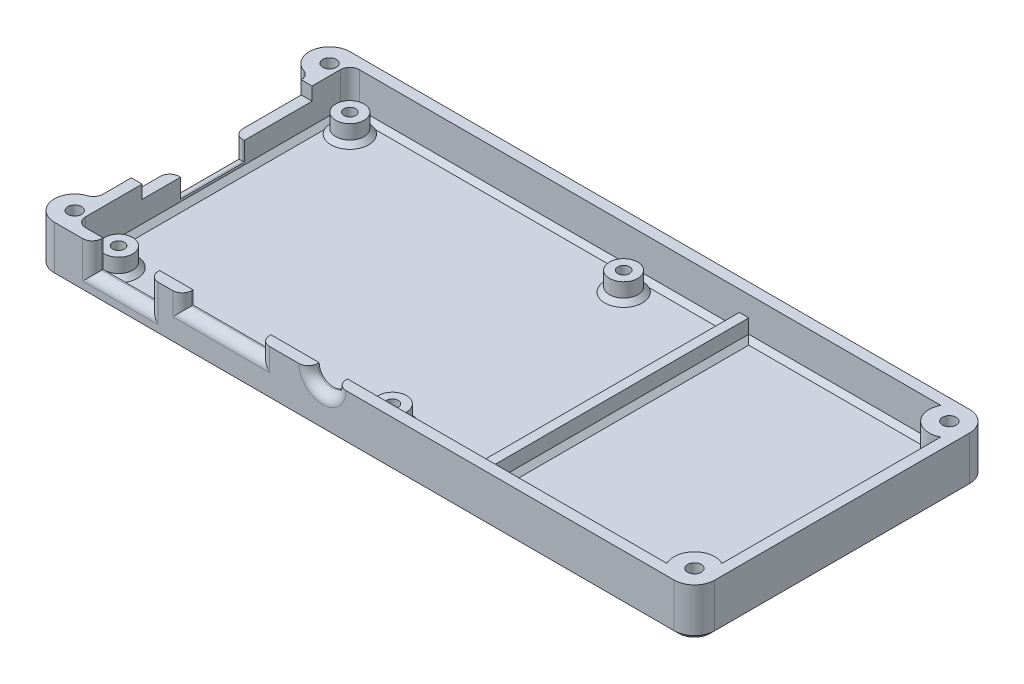
SolidWorks part; units mm, degrees
ref_plane "Front Plane" through (0, 0, 0) normal (0, 0, 1) x (1, 0, 0)
ref_plane "Top Plane" through (0, 0, 0) normal (0, 1, 0) x (1, 0, 0)
ref_plane "Right Plane" through (0, 0, 0) normal (1, 0, 0) x (0, 0, -1)
sketch "Sketch1" plane through (0, 0, 0) normal (0, 1, 0) x (1, 0, 0)
  line L0 (-71.5618, 3.106) -> (57.4382, 3.106) construction
  line L1 (-71.5618, 31.106) -> (57.4382, 31.106)
  line L2 (-71.5618, 31.106) -> (-71.5618, -24.894)
  line L3 (-71.5618, -24.894) -> (57.4382, -24.894)
  line L4 (57.4382, 31.106) -> (57.4382, -24.894)
  line L5 (-60.6618, -24.894) -> (-60.6618, -31.6828) construction
  line L6 (-68.0618, 27.606) -> (-10.0618, 27.606)
  line L7 (-68.0618, 27.606) -> (-68.0618, -21.394)
  line L8 (-68.0618, -21.394) -> (-10.0618, -21.394)
  line L9 (-10.0618, 27.606) -> (-10.0618, -21.394)
  line L10 (-39.5618, -24.894) -> (-39.5618, -31.6828) construction
  line L11 (-18.0618, -24.894) -> (-18.0618, -31.6828) construction
  line L12 (-65.4118, -26.5648) -> (-55.9118, -26.5648) construction
  line L13 (-48.0618, -26.5648) -> (-31.0618, -26.5648) construction
  line L14 (-22.0618, -26.5648) -> (-14.0618, -26.5648) construction
  line L15 (-72.5618, 9.606) -> (-72.5618, -3.394) construction
  line L16 (-71.5618, 3.106) -> (-72.5618, 3.106) construction
  dimension "D1" = 129
  dimension "D2" = 56
  dimension "D3" = 49
  dimension "D4" = 58
  dimension "D5" = 3.5
  dimension "D6" = 3.5
  dimension "D7" = 10.9
  dimension "D8" = 32
  dimension "D9" = 53.5
  dimension "D10" = 2
  dimension "D11" = 13
  dimension "D12" = 9.5
  dimension "D13" = 17
  dimension "D14" = 8
sketch "Sketch3" plane through (0, 0, 0) normal (0, 1, 0) x (1, 0, 0)
  line L4 (60.7382, 34.406) -> (-74.8618, 34.406)
  line L5 (-74.8618, 34.406) -> (-74.8618, -28.194)
  line L6 (-74.8618, -28.194) -> (60.7382, -28.194)
  line L7 (60.7382, -28.194) -> (60.7382, 34.406)
  line L8 (58.4382, 32.106) -> (-72.5618, 32.106)
  line L9 (58.4382, -25.894) -> (58.4382, 32.106)
  line L10 (-72.5618, -25.894) -> (58.4382, -25.894)
  line L11 (-72.5618, 32.106) -> (-72.5618, -25.894)
  line L12 (58.4382, 32.106) -> (-72.5618, 32.106)
  line L13 (58.4382, -25.894) -> (58.4382, 32.106)
  line L14 (-72.5618, -25.894) -> (58.4382, -25.894)
  line L15 (-72.5618, 32.106) -> (-72.5618, -25.894)
  line L16 (-7.0618, 3.106) -> (-7.0618, 34.406) construction
  line L17 (-71.5618, 3.106) -> (57.4382, 3.106) construction
  line L20 (-74.8618, 3.106) -> (52.7382, 3.106) construction
  line L25 (60.7382, -28.194) -> (60.7382, 34.406) construction
  line L26 (58.4382, -25.894) -> (58.4382, 32.106) construction
  dimension "D1" = 1
  dimension "D2" = 2.3
extrude "Boss-Extrude1" add sketch "Sketch3" along normal blind 10.3
sketch "Sketch5" plane through (0, 0, 0) normal (0, 1, 0) x (1, 0, 0)
  line L1 (-72.5618, 32.106) -> (58.4382, 32.106)
  line L2 (-72.5618, 32.106) -> (-72.5618, -25.894)
  line L3 (-72.5618, -25.894) -> (58.4382, -25.894)
  line L4 (58.4382, 32.106) -> (58.4382, -25.894)
extrude "Boss-Extrude2" add sketch "Sketch5" along normal blind 2
sketch "Sketch6" plane through (0, 2, 0) normal (0, 1, 0) x (1, 0, 0)
  circle A0 centre (-68.0618, 27.606) radius 3
  circle A1 centre (-68.0618, -21.394) radius 3
  circle A2 centre (-10.0618, -21.394) radius 3
  circle A3 centre (-10.0618, 27.606) radius 3
extrude "Boss-Extrude3" add sketch "Sketch6" along normal blind 4
hole_wizard "Ø2.5 (2.5) Diameter Hole1" positions "Sketch8" profile "Sketch9" hole size "Ø2.5" standard "ANSI Metric"
sketch "Sketch8" plane through (0, 6, 0) normal (0, 1, 0) x (1, 0, 0)
  point P0 (-68.0618, 27.606)
  point P3 (-10.0618, 27.606)
  point P6 (-10.0618, -21.394)
  point P9 (-68.0618, -21.394)
sketch "Sketch9" plane through (-68.0618, 6, -27.606) normal (1, 0, 0) x (0, 0, 1)
  line L0 (0, 0) -> (0, 8.7511)
  line L1 (0, 8.7511) -> (1.25, 8)
  line L2 (1.25, 8) -> (1.25, 0)
  line L5 (1.25, 0) -> (0, 0)
  line L10 (0, 8.7511) -> (-1.25, 8) construction
  line L11 (0, -6.35) -> (0, 107.95) construction
  dimension "Hole Dia." = 2.5
  dimension "Hole Depth" = 8
  dimension "Drill Angle" = 118
sketch "Sketch10" plane through (0, 2, 0) normal (0, 1, 0) x (1, 0, 0)
  line L0 (58.4382, 32.106) -> (-72.5618, 32.106) construction
  line L1 (9.9382, 32.106) -> (11.9382, 32.106)
  line L2 (9.9382, 32.106) -> (9.9382, -25.894)
  line L3 (9.9382, -25.894) -> (11.9382, -25.894)
  line L4 (11.9382, 32.106) -> (11.9382, -25.894)
  line L5 (-72.5618, -25.894) -> (58.4382, -25.894) construction
  line L6 (-10.0618, 27.606) -> (-10.0618, -21.394) construction
  dimension "D1" = 2
  dimension "D2" = 20
extrude "Boss-Extrude4" add sketch "Sketch10" along normal blind 4
sketch "Sketch11" plane through (0, 0, 28.194) normal (0, 0, 1) x (1, 0, 0)
  line L0 (-74.8618, 10.3) -> (-74.8618, 0) construction
  line L1 (-66.8618, 10.3) -> (-54.8618, 10.3)
  line L2 (-66.8618, 10.3) -> (-66.8618, 4.5)
  line L3 (-66.8618, 4.5) -> (-54.8618, 4.5)
  line L4 (-54.8618, 10.3) -> (-54.8618, 4.5)
  line L5 (-74.8618, 0) -> (60.7382, 0) construction
  line L6 (-60.8618, 10.3) -> (-60.6618, 0) construction
  line L7 (-65.4118, 0) -> (-55.9118, 0) construction
  line L9 (-47.778, 10.3) -> (-31.278, 10.3)
  line L10 (-47.778, 10.3) -> (-47.778, 7.5)
  line L11 (-47.778, 7.5) -> (-31.278, 7.5)
  line L12 (-31.278, 10.3) -> (-31.278, 7.5)
  line L13 (-68.0618, 0) -> (-10.0618, 0) construction
  line L14 (-39.5618, 0) -> (-39.528, 10.3) construction
  line L15 (-48.0618, 0) -> (-31.0618, 0) construction
  line L16 (-18.0618, 0) -> (-18.0618, 10.3) construction
  line L17 (-22.0618, 0) -> (-14.0618, 0) construction
  line L18 (-74.8618, 10.3) -> (60.7382, 10.3) construction
  circle A0 centre (-18.0618, 10.3) radius 3
  dimension "D5" = 6
  dimension "D1" = 4.5
  dimension "D2" = 12
  dimension "D3" = 7.5
  dimension "D4" = 16.5
  dimension "D6" = 8
extrude "Cut-Extrude1" cut sketch "Sketch11" against normal up to next
sketch "Sketch12" plane through (-74.8618, 0, 0) normal (-1, 0, 0) x (0, 0, 1)
  line L0 (-3.106, 0) -> (-3.106, 10.3) construction
  line L1 (-27.606, 0) -> (21.394, 0) construction
  line L2 (-34.406, 10.3) -> (28.194, 10.3) construction
  line L4 (-9.7329, 10.3) -> (3.7671, 10.3)
  line L5 (-9.7329, 10.3) -> (-9.7329, 3.5)
  line L6 (-9.7329, 3.5) -> (3.7671, 3.5)
  line L7 (3.7671, 10.3) -> (3.7671, 3.5)
  line L8 (-24.106, 10.3) -> (11.894, 10.3)
  line L9 (-24.106, 10.3) -> (-24.106, 7.5)
  line L10 (-24.106, 7.5) -> (11.894, 7.5)
  line L11 (11.894, 10.3) -> (11.894, 7.5)
  dimension "D1" = 13.5
  dimension "D2" = 3.5
  dimension "D3" = 7.5
  dimension "D4" = 36
extrude "Cut-Extrude2" cut sketch "Sketch12" against normal up to next contours L10 L11 L8 L9 | L7 L6 L5 L4
fillet "Fillet6" radius 2 1 edges at (58.4382, 6.15, -32.106)
fillet "Fillet8" radius 2 2 edges at (-72.5618, 6.15, 25.894) (-72.5618, 6.15, -32.106)
chamfer "Chamfer1" distance 1 angle 45 4 edges at (-68.0618, 2, 24.394) (-10.0618, 2, 24.394) (-10.0618, 2, -24.606) (-68.0618, 2, -24.606)
fillet "Fillet9" radius 2 9 edges at (-74.8618, 5.5, -9.7329) (-74.8618, 3.5, -2.9829) (-74.8618, 5.5, 3.7671) (-18.0618, 7.3, 28.194) (-31.278, 8.9, 28.194) (-47.778, 8.9, 28.194) (-39.528, 7.5, 28.194) (-54.8618, 7.4, 28.194) (-60.8618, 4.5, 28.194)
sketch "Sketch17" plane through (0, 0, 0) normal (0, 1, 0) x (1, 0, 0)
  line L0 (-74.8618, 34.406) -> (-74.8618, 24.106) construction
  line L1 (-74.8618, 34.406) -> (-74.8618, 25.806)
  line L2 (-74.8618, 25.806) -> (-74.659, 25.9406)
  line L3 (-74.8618, -19.594) -> (-74.8618, -28.194)
  line L4 (-74.8618, -28.194) -> (-74.659, -28.0594)
  arc A0 (-74.8618, -19.594) -> (-74.8618, -28.194) centre (-74.8618, -23.894) ccw
  arc A1 (-74.8618, 34.406) -> (-74.8618, 25.806) centre (-74.8618, 30.106) ccw
extrude "Boss-Extrude6" add sketch "Sketch17" along normal up to vertex (10.3 mm away) contours L1 A1 | L3 A0 region at (-76.6867, 0, -30.106) region at (-76.6867, 0, 23.894) up to point (-74.8618, 10.3, 28.194)
hole_wizard "Ø2.9 (2.9) Diameter Hole2" positions "Sketch19" profile "Sketch18" hole size "Ø2.9" standard "ANSI Metric" end condition up to next
sketch "Sketch19" plane through (0, 10.3, 0) normal (0, 1, 0) x (1, 0, 0)
  point P0 (-74.8618, 30.106)
sketch "Sketch18" plane through (-74.8618, 10.3, -30.106) normal (1, 0, 0) x (0, 0, 1)
  line L0 (0, 0) -> (0, 10.3)
  line L1 (0, 10.3) -> (1.45, 10.3)
  line L2 (1.45, 10.3) -> (1.45, 0)
  line L5 (1.45, 0) -> (0, 0)
  line L11 (0, -6.35) -> (0, 107.95) construction
  dimension "Thru Hole Dia." = 2.9
  dimension "Thru Hole Depth" = 10.3
hole_wizard "Ø2.9 (2.9) Diameter Hole1" positions "Sketch21" profile "Sketch20" hole size "Ø2.9" standard "ANSI Metric" end condition up to next
sketch "Sketch21" plane through (0, 10.3, 0) normal (0, 1, 0) x (1, 0, 0)
  point P0 (-74.8618, -23.894)
sketch "Sketch20" plane through (-74.8618, 10.3, 23.894) normal (1, 0, 0) x (0, 0, 1)
  line L0 (0, 0) -> (0, 10.3)
  line L1 (0, 10.3) -> (1.45, 10.3)
  line L2 (1.45, 10.3) -> (1.45, 0)
  line L5 (1.45, 0) -> (0, 0)
  line L11 (0, -6.35) -> (0, 107.95) construction
  dimension "Thru Hole Dia." = 2.9
  dimension "Thru Hole Depth" = 10.3
sketch "Sketch24" plane through (0, 2, 0) normal (0, 1, 0) x (1, 0, 0)
  line L0 (11.9382, 3.106) -> (61.5789, 3.106) construction
  line L1 (11.9382, -25.894) -> (11.9382, 32.106) construction
  line L2 (60.7382, -28.194) -> (60.7382, 34.406) construction
  circle A0 centre (56.4382, -23.894) radius 4.3
  circle A1 centre (56.4382, 30.106) radius 4.3
  dimension "D1" = 4.3
extrude "Boss-Extrude7" add sketch "Sketch24" along normal up to surface (8.3 mm away) up to face at (-74.8618, 10.3, -28.656)
hole_wizard "Ø2.9 (2.9) Diameter Hole5" positions "Sketch31" profile "Sketch30" hole size "Ø2.9" standard "ANSI Metric" end condition up to next
sketch "Sketch31" plane through (0, 10.3, 0) normal (0, 1, 0) x (1, 0, 0)
  point P0 (56.4382, -23.894)
sketch "Sketch30" plane through (56.4382, 10.3, 23.894) normal (1, 0, 0) x (0, 0, 1)
  line L0 (0, 0) -> (0, 10.3)
  line L1 (0, 10.3) -> (1.45, 10.3)
  line L2 (1.45, 10.3) -> (1.45, 0)
  line L5 (1.45, 0) -> (0, 0)
  line L11 (0, -6.35) -> (0, 107.95) construction
  dimension "Thru Hole Dia." = 2.9
  dimension "Thru Hole Depth" = 10.3
hole_wizard "Ø2.9 (2.9) Diameter Hole4" positions "Sketch28" profile "Sketch27" hole size "Ø2.9" standard "ANSI Metric" end condition up to next
sketch "Sketch28" plane through (0, 10.3, 0) normal (0, 1, 0) x (1, 0, 0)
  point P0 (56.4382, 30.106)
sketch "Sketch27" plane through (56.4382, 10.3, -30.106) normal (1, 0, 0) x (0, 0, 1)
  line L0 (0, 0) -> (0, 10.3)
  line L1 (0, 10.3) -> (1.45, 10.3)
  line L2 (1.45, 10.3) -> (1.45, 0)
  line L5 (1.45, 0) -> (0, 0)
  line L11 (0, -6.35) -> (0, 107.95) construction
  dimension "Thru Hole Dia." = 2.9
  dimension "Thru Hole Depth" = 10.3
fillet "Fillet10" radius 4.3 1 edges at (60.7382, 5.15, -34.406)
fillet "Fillet18" radius 2 2 edges at (-74.8618, 5.15, 19.594) (-74.8618, 5.15, -25.806)
chamfer "Chamfer3" distance 1 angle 45 9 edges at (59.4788, 0, -33.1466) (-9.2118, 0, -34.406) (60.7382, 0, -0.956) (-79.1058, 0, -30.7975) (-75.2385, 0, -25.3002) (-74.8618, 0, -3.106) (-75.2385, 0, 19.0883) (-79.1058, 0, 24.5855) (-7.0618, 0, 28.194)
fillet "Fillet19" radius 2 1 edges at (-66.8618, 6.4, 28.194)
fillet "Fillet20" radius 4.3 1 edges at (60.7382, 5.65, 28.194)
chamfer "Chamfer5" distance 1 angle 45 8 edges at (-72.5618, 2, -3.106) (-71.976, 2, 25.3082) (-71.976, 2, -31.5202) (-30.3118, 2, 25.894) (-30.3118, 2, -32.106) (9.9382, 2, -3.106) (11.9382, 2, -3.106) (32.2849, 2, -32.106)
chamfer "Chamfer6" distance 1 angle 45 1 edges at (58.4382, 2, -3.106)
chamfer "Chamfer7" distance 1 angle 45 1 edges at (59.4788, 0, 26.9346)
